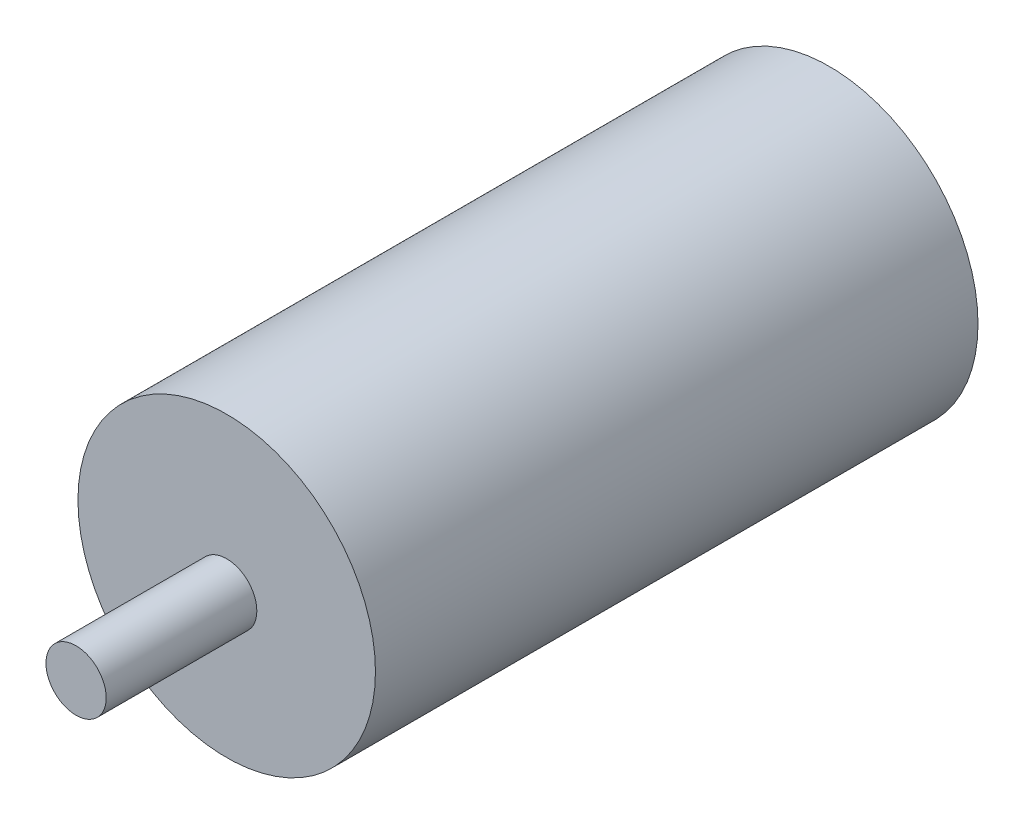
SolidWorks part; units mm, degrees
ref_plane "Front Plane" through (0, 0, 0) normal (0, 0, 1) x (1, 0, 0)
ref_plane "Top Plane" through (0, 0, 0) normal (0, 1, 0) x (1, 0, 0)
ref_plane "Right Plane" through (0, 0, 0) normal (1, 0, 0) x (0, 0, -1)
sketch "Sketch1" plane through (0, 0, 0) normal (0, 0, 1) x (1, 0, 0)
  circle A0 centre (0, 0) radius 19.75
  dimension "D1" = 39.5
extrude "Boss-Extrude1" add sketch "Sketch1" along normal blind 80
sketch "Sketch2" plane through (0, 0, 80) normal (0, 0, 1) x (1, 0, 0)
  circle A0 centre (0, -0.8743) radius 4
  dimension "D1" = 8
extrude "Boss-Extrude2" add sketch "Sketch2" along normal blind 20
